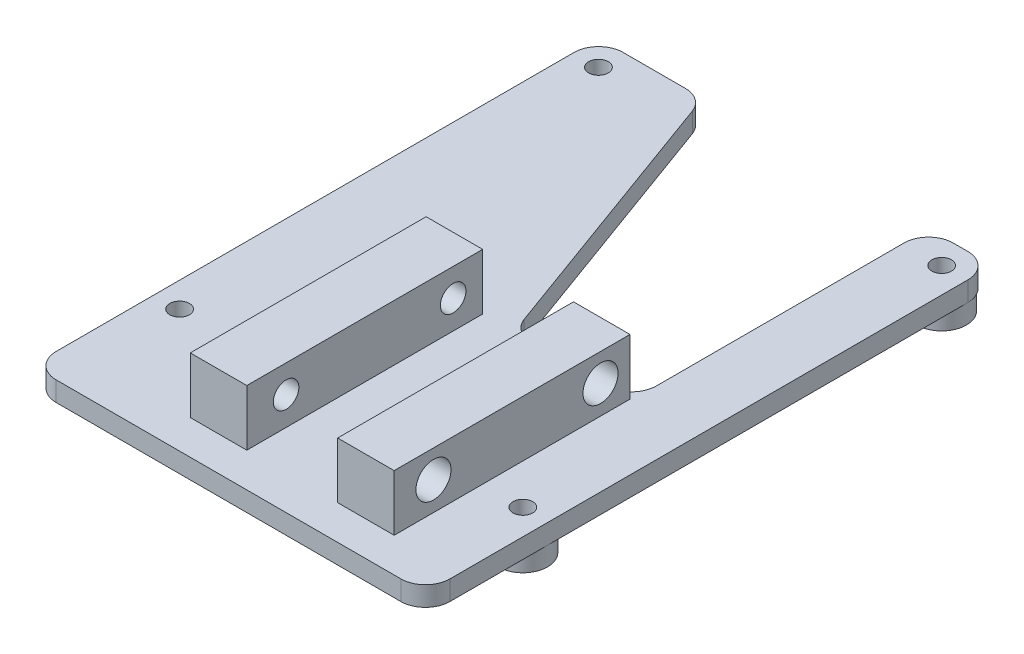
SolidWorks part; units mm, degrees
material "Onyx w/ CF"
ref_plane "Front Plane" through (0, 0, 0) normal (0, 0, 1) x (1, 0, 0)
ref_plane "Top Plane" through (0, 0, 0) normal (0, 1, 0) x (1, 0, 0)
ref_plane "Right Plane" through (0, 0, 0) normal (1, 0, 0) x (0, 0, -1)
sketch "Sketch1" plane through (0, 0, 0) normal (0, 1, 0) x (1, 0, 0)
  line L1 (-10.373, 12) -> (10.373, 12)
  line L2 (-10.373, 12) -> (-10.373, -12)
  line L3 (-10.373, -12) -> (10.373, -12)
  line L4 (10.373, 12) -> (10.373, -12)
  line L5 (-10.373, 12) -> (10.373, -12) construction
  line L6 (-10.373, -12) -> (10.373, 12) construction
  point P0 (0, 0)
  dimension "D1" = 20.746
  dimension "D2" = 24
extrude "Boss-Extrude1" add sketch "Sketch1" along normal blind 5.7
sketch "Sketch9" plane through (0, 0, 0) normal (0, -1, 0) x (1, 0, 0)
  line L0 (-10.373, 12) -> (10.373, 12) construction
  line L1 (4.623, -12) -> (-4.623, -12)
  line L2 (4.623, -12) -> (4.623, 12)
  line L3 (4.623, 12) -> (-4.623, 12)
  line L4 (-4.623, -12) -> (-4.623, 12)
  line L5 (4.623, -12) -> (-4.623, 12) construction
  line L6 (4.623, 12) -> (-4.623, -12) construction
  line L7 (10.373, -12) -> (-10.373, -12) construction
  line L8 (10.373, 12) -> (10.373, -12) construction
  point P0 (0, 0)
  dimension "D1" = 5.75
extrude "Cut-Extrude3" cut sketch "Sketch9" against normal through all
hole_wizard "9/64 (0.14063) Diameter Hole1" positions "Sketch6" profile "Sketch7" hole size "9/64" standard "ANSI Inch"
sketch "Sketch6" plane through (10.373, 0, 0) normal (1, 0, 0) x (0, 0, -1)
  line L4 (9, 2.9) -> (-8, 2.9) construction
  line L7 (-12, 5.7) -> (12, 5.7) construction
  line L9 (-12, 5.7) -> (-12, 0) construction
  line L10 (-8, 2.9) -> (9, 2.9) construction
  point P0 (9, 2.9)
  point P2 (-8, 2.9)
  dimension "D1" = 4
  dimension "D2" = 2.8
  dimension "D3" = 17
sketch "Sketch7" plane through (10.373, 2.9, -9) normal (0, 1, 0) x (0, 0, -1)
  line L0 (0, 0) -> (0, 6.8231)
  line L1 (0, 6.8231) -> (1.786, 5.75)
  line L2 (1.786, 5.75) -> (1.786, 0)
  line L5 (1.786, 0) -> (0, 0)
  line L10 (0, 6.8231) -> (-1.786, 5.75) construction
  line L11 (0, -6.35) -> (0, 107.95) construction
  dimension "Hole Dia." = 3.572
  dimension "Hole Depth" = 5.75
  dimension "Drill Angle" = 118
sketch "Sketch8" plane through (-10.373, 0, 0) normal (-1, 0, 0) x (0, 0, 1)
  line L0 (8, 2.9) -> (-9, 2.9) construction
  line L1 (-12, 5.7) -> (12, 5.7) construction
  line L3 (12, 5.7) -> (12, 0) construction
  circle A0 centre (8, 2.9) radius 1.3
  circle A1 centre (-9, 2.9) radius 1.3
  dimension "D1" = 2.8
  dimension "D4" = 2.6
  dimension "D2" = 17
  dimension "D3" = 4
extrude "Cut-Extrude2" cut sketch "Sketch8" against normal up to surface (5.75 mm away) up to face at (-4.623, 2.85, 0)
sketch "Sketch10" plane through (0, 0, 0) normal (0, -1, 0) x (1, 0, 0)
  line L0 (4.623, 12) -> (10.373, 12) construction
  line L1 (17.053, 15.5) -> (-23.027, 15.5)
  line L2 (17.053, 15.5) -> (17.053, -42.2)
  line L3 (17.053, -42.2) -> (-23.027, -42.2)
  line L4 (-23.027, 15.5) -> (-23.027, -42.2)
  line L5 (10.373, 12) -> (10.373, -12) construction
  dimension "D1" = 40.08
  dimension "D2" = 57.7
  dimension "D3" = 3.5
  dimension "D4" = 6.68
extrude "Boss-Extrude2" add sketch "Sketch10" along normal blind 2
sketch "Sketch11" plane through (0, -2, 0) normal (0, -1, 0) x (1, 0, 0)
  line L0 (-23.027, 15.5) -> (-23.027, -42.2) construction
  line L1 (17.053, 15.5) -> (-23.027, 15.5) construction
  line L2 (17.053, -42.2) -> (17.053, 15.5) construction
  line L3 (-23.027, -42.2) -> (17.053, -42.2) construction
  circle A0 centre (14.453, 2.985) radius 2.515
  circle A1 centre (-20.475, 2.985) radius 2.515
  circle A2 centre (14.45, -39.6362) radius 2.515
  circle A3 centre (-20.475, -39.6362) radius 2.515
  point P8 (-20.475, 12.9)
  point P9 (0, 0)
  point P14 (0, 0)
  point P15 (0, 0)
  dimension "D1" = 5.03
  dimension "D2" = 2.6
  dimension "D3" = 2.552
  dimension "D4" = 2.5638
  dimension "D5" = 2.603
  dimension "D6" = 2.5638
  dimension "D7" = 2.552
  dimension "D8" = 12.515
extrude "Boss-Extrude3" add sketch "Sketch11" along normal blind 2
sketch "Sketch12" plane through (0, -4, 0) normal (0, -1, 0) x (1, 0, 0)
  circle A0 centre (14.453, 2.985) radius 1
  circle A1 centre (-20.475, 2.985) radius 1
  circle A2 centre (-20.475, -39.6362) radius 1
  circle A3 centre (14.45, -39.6362) radius 1
  circle A4 centre (-20.475, -39.6362) radius 2.515 construction
  circle A5 centre (14.45, -39.6362) radius 2.515 construction
  circle A6 centre (14.453, 2.985) radius 2.515 construction
  circle A7 centre (-20.475, 2.985) radius 2.515 construction
  dimension "D1" = 2
extrude "Cut-Extrude4" cut sketch "Sketch12" against normal through all
fillet "Fillet2" radius 2.5 4 edges at (17.053, -1, -42.2) (-23.027, -1, -42.2) (-23.027, -1, 15.5) (17.053, -1, 15.5)
sketch "Sketch14" plane through (0, 0, 0) normal (0, 1, 0) x (1, 0, 0)
  line L4 (10.553, 42.2) -> (10.553, 12)
  line L5 (10.553, 12) -> (-1.447, 12)
  line L6 (-1.447, 12) -> (-12.4389, 42.2)
  line L7 (-20.527, 42.2) -> (14.553, 42.2) construction
  line L8 (10.373, 12) -> (4.623, 12) construction
  line L9 (-12.4389, 42.2) -> (10.553, 42.2)
  dimension "D1" = 4
  dimension "D2" = 12
  dimension "D3" = 20
extrude "Cut-Extrude5" cut sketch "Sketch14" against normal through all
fillet "Fillet3" radius 2.5 4 edges at (10.553, -1, -12) (-1.447, -1, -12) (10.553, -1, -42.2) (-12.4389, -1, -42.2)
sketch "Sketch15" plane through (0, 5.7, 0) normal (0, 1, 0) x (1, 0, 0)
  line L0 (8.053, 12) -> (10.373, 12)
  line L1 (8.053, 12) -> (4.623, 12) construction
  line L2 (10.373, -12) -> (10.373, 13.5685) construction
  line L3 (10.373, 12) -> (10.373, 13.5685)
  arc A0 (8.053, 12) -> (10.373, 13.5685) centre (8.053, 14.5) ccw construction
  arc A1 (10.373, 13.5685) -> (8.053, 12) centre (8.053, 14.5) cw
extrude "Cut-Extrude6" cut sketch "Sketch15" against normal up to surface (5.7 mm away) up to face at (0.6321, 0, -16.5094)
